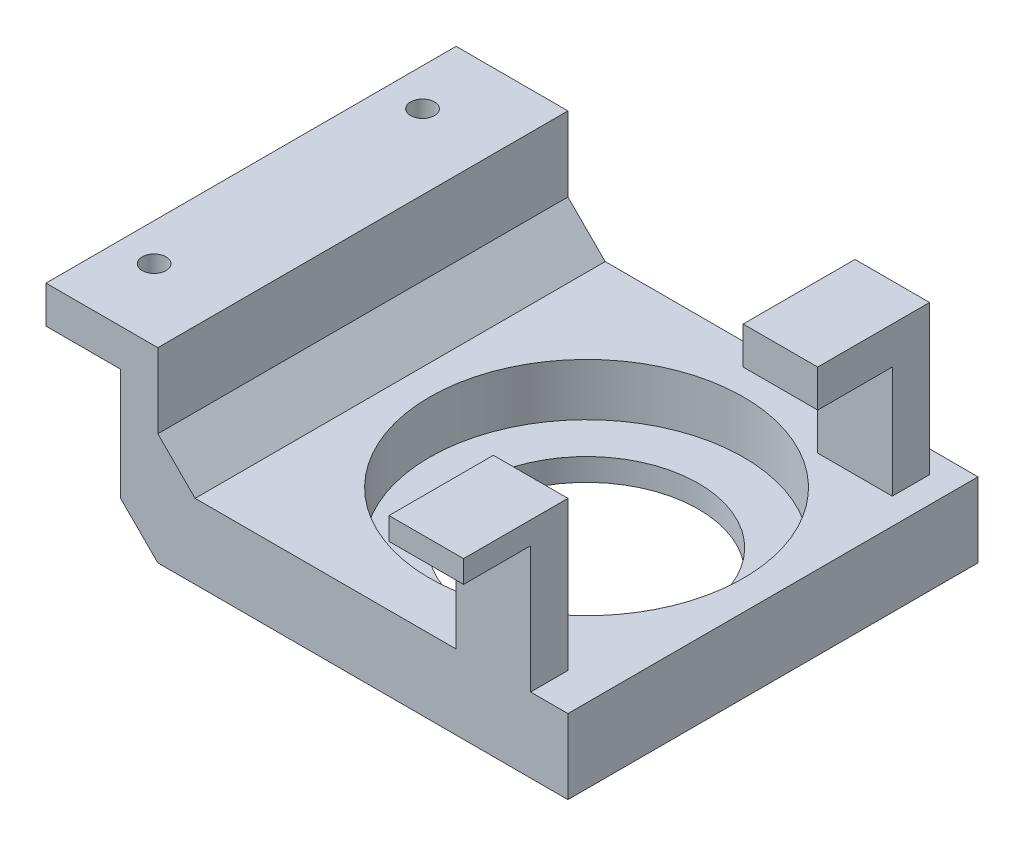
SolidWorks part; units mm, degrees
ref_plane "Alzado" through (0, 0, 0) normal (0, 0, 1) x (1, 0, 0)
ref_plane "Planta" through (0, 0, 0) normal (0, 1, 0) x (1, 0, 0)
ref_plane "Vista lateral" through (0, 0, 0) normal (1, 0, 0) x (0, 0, -1)
sketch "Croquis4" plane through (0, 0, 0) normal (0, 0, 1) x (1, 0, 0)
  line L0 (-31.4286, 5.7619) -> (-31.4286, 14.7619)
  line L5 (-26.4286, 4.7619) -> (28.5714, 4.7619)
  line L6 (-31.4286, 5.7619) -> (-31.4286, -5.2381)
  line L7 (-31.4286, -5.2381) -> (28.5714, -5.2381)
  line L8 (28.5714, 4.7619) -> (28.5714, -5.2381)
  line L9 (-31.4286, 5.7619) -> (28.5714, -5.2381) construction
  line L10 (-31.4286, -5.2381) -> (28.5714, 4.7619) construction
  line L11 (-31.4286, 14.7619) -> (-41.4286, 14.7619)
  line L12 (-41.4286, 14.7619) -> (-41.4286, 19.7619)
  line L13 (-41.4286, 19.7619) -> (-26.4286, 19.7619)
  line L14 (-26.4286, 19.7619) -> (-26.4286, 4.7619)
  point P0 (0, 0)
  dimension "D1" = 11
  dimension "D2" = 60
  dimension "D3" = 5
  dimension "D4" = 5
  dimension "D5" = 10
  dimension "D6" = 10
  dimension "D7" = 15
extrude "Saliente-Extruir2" add sketch "Croquis4" along normal blind 55
sketch "Croquis6" plane through (0, 4.7619, 0) normal (0, 1, 0) x (1, 0, 0)
  line L1 (28.5714, -55) -> (28.5714, 0) construction
  line L2 (28.5714, -27.5) -> (-26.4286, -27.5) construction
  line L3 (-26.4286, -55) -> (-26.4286, 0) construction
  circle A0 centre (3.5714, -27.5) radius 21.05
  dimension "D1" = 42.1
  dimension "D3" = 25
extrude "Cortar-Extruir1" cut sketch "Croquis6" against normal blind 7
sketch "Croquis8" plane through (0, -2.2381, 0) normal (0, 1, 0) x (1, 0, 0)
  circle A0 centre (3.5714, -27.5) radius 15
  dimension "D1" = 30
extrude "Cortar-Extruir2" cut sketch "Croquis8" against normal through all both and the other way through all
sketch "Croquis9" plane through (0, 14.7619, 0) normal (0, -1, 0) x (1, 0, 0)
  line L0 (-41.4286, 27.5) -> (-31.4286, 27.5) construction
  line L1 (-41.4286, 55) -> (-41.4286, 0) construction
  line L2 (-31.4286, 55) -> (-31.4286, 0) construction
  line L3 (-36.4286, 27.5) -> (-36.4286, 61.1151) construction
  circle A0 centre (-36.4286, 45.5) radius 1.6
  circle A2 centre (-36.4286, 9.5) radius 1.6
  dimension "D1" = 18
  dimension "D2" = 3.2
extrude "Cortar-Extruir3" cut sketch "Croquis9" against normal through all both and the other way through all
chamfer "Chaflán1" distance 5 angle 45 2 edges at (-26.4286, 4.7619, 27.5) (-31.4286, -5.2381, 27.5)
sketch "Croquis11" plane through (0, 4.7619, 0) normal (0, 1, 0) x (1, 0, 0)
  line L1 (28.5714, -55) -> (28.5714, 0) construction
  line L6 (28.5714, -27.5) -> (-21.4286, -27.5) construction
  line L7 (-21.4286, 0) -> (-21.4286, -55) construction
  line L12 (23.5714, -55) -> (23.5714, -50)
  line L13 (28.5714, -55) -> (-21.4286, -55) construction
  line L14 (23.5714, -50) -> (13.5714, -50)
  line L15 (13.5714, -50) -> (13.5714, -55)
  line L16 (13.5714, -55) -> (23.5714, -55)
  dimension "D1" = 10
  dimension "D2" = 5
  dimension "D3" = 5
extrude "Saliente-Extruir3" add sketch "Croquis11" along normal blind 20
sketch "Croquis12" plane through (0, 0, 55) normal (0, 0, 1) x (1, 0, 0)
  line L7 (13.5714, 24.7619) -> (13.5714, 21.7619)
  line L8 (13.5714, 24.7619) -> (23.5714, 24.7619) construction
  line L9 (13.5714, 24.7619) -> (13.5714, 4.7619) construction
  line L10 (13.5714, 21.7619) -> (23.5714, 21.7619)
  line L11 (23.5714, 24.7619) -> (23.5714, 4.7619) construction
  line L12 (23.5714, 21.7619) -> (23.5714, 24.7619)
  line L13 (23.5714, 24.7619) -> (13.5714, 24.7619)
  dimension "D1" = 3
extrude "Saliente-Extruir4" add sketch "Croquis12" along normal blind 9
sketch "Croquis13" plane through (0, 4.7619, 0) normal (0, 1, 0) x (1, 0, 0)
  line L0 (25.0714, -8) -> (25.0714, -3)
  line L1 (25.0714, -3) -> (15.0714, -3)
  line L2 (15.0714, -3) -> (15.0714, -8)
  line L3 (15.0714, -8) -> (25.0714, -8)
  line L4 (25.0714, -9) -> (25.0714, 2.2982) construction
  line L5 (25.0714, -9) -> (-6.9286, -9) construction
  dimension "D1" = 5
  dimension "D2" = 10
  dimension "D3" = 1
extrude "Saliente-Extruir5" add sketch "Croquis13" along normal blind 20
sketch "Croquis14" plane through (0, 0, 8) normal (0, 0, 1) x (1, 0, 0)
  line L0 (15.0714, 24.7619) -> (25.0714, 24.7619)
  line L1 (25.0714, 24.7619) -> (25.0714, 19.7619)
  line L2 (25.0714, 24.7619) -> (25.0714, 4.7619) construction
  line L3 (25.0714, 19.7619) -> (15.0714, 19.7619)
  line L4 (15.0714, 24.7619) -> (15.0714, 4.7619) construction
  line L5 (15.0714, 19.7619) -> (15.0714, 24.7619)
  dimension "D1" = 5
extrude "Saliente-Extruir6" add sketch "Croquis14" along normal blind 10
